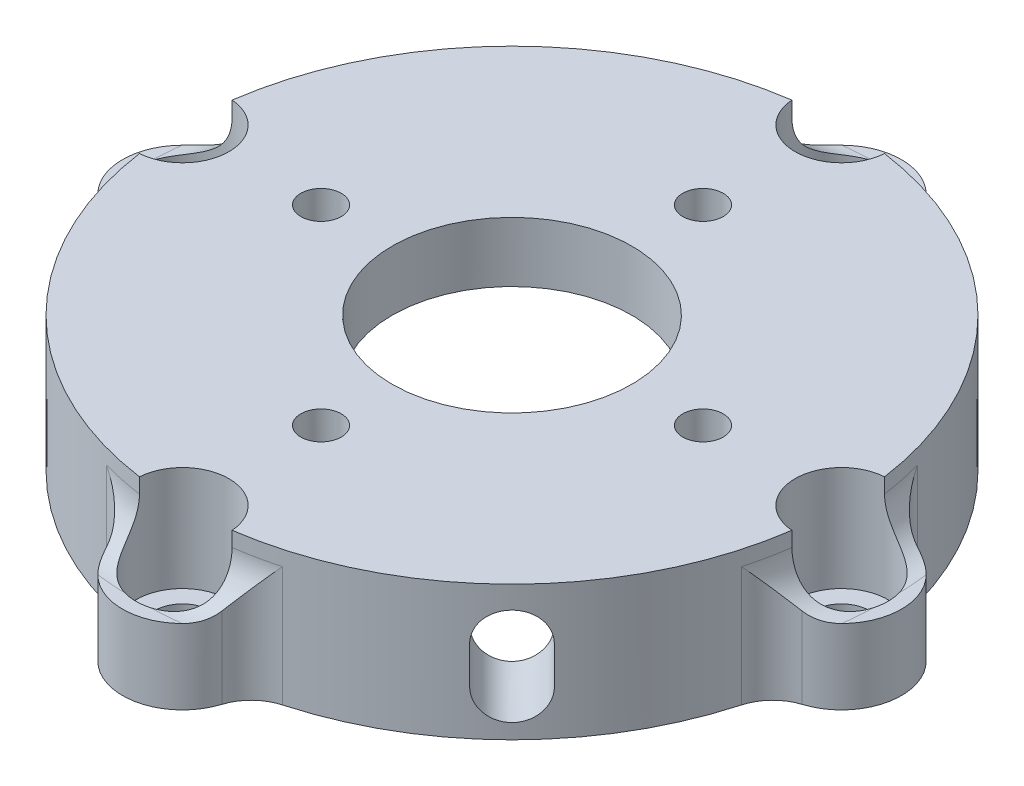
SolidWorks part; units mm, degrees
note: The reader was unsure of these and kept them because the rebuilt part matched: shared geometry of "Sketch4<5>", "Sketch4<6>", "Sketch4<7>", "Sketch5<4>".
ref_plane "Front Plane" through (0, 0, 0) normal (0, 0, 1) x (1, 0, 0)
ref_plane "Top Plane" through (0, 0, 0) normal (0, 1, 0) x (1, 0, 0)
ref_plane "Right Plane" through (0, 0, 0) normal (1, 0, 0) x (0, 0, -1)
sketch "Sketch1" plane through (0, 0, 0) normal (0, 1, 0) x (1, 0, 0)
  circle A0 centre (0, 0) radius 22
  circle A1 centre (0, 0) radius 8
  dimension "D1" = 44
  dimension "D2" = 16
extrude "Boss-Extrude1" add sketch "Sketch1" against normal blind 4
sketch "Sketch2" plane through (0, -4, 0) normal (0, -1, 0) x (1, 0, 0)
  circle A0 centre (0, 0) radius 22
  circle A1 centre (0, 0) radius 22 construction
  circle A2 centre (0, 0) radius 17
  dimension "D1" = 5
extrude "Boss-Extrude4" add sketch "Sketch2" along normal blind 5
sketch "Sketch4" plane through (0, -9, 0) normal (0, -1, 0) x (1, 0, 0)
  circle A0 centre (0, 0) radius 22 construction
  circle A1 centre (0, 22) radius 3.1
  circle A2 centre (0, 22) radius 1.85
  circle A3 centre (0, 22) radius 4
  dimension "D1" = 44
  dimension "D2" = 6.2
  dimension "D3" = 3.7
  dimension "D4" = 8
extrude "Boss-Extrude2" add sketch "Sketch4" against normal blind 5
extrude "Boss-Extrude3" add sketch "Sketch4<5>" against normal blind 2
sketch "Sketch4<5>" plane through (0, -9, 0) normal (0, -1, 0) x (1, 0, 0) same geometry as "Sketch4"
extrude "Cut-Extrude3" cut sketch "Sketch4<6>" against normal through all from surface at -2 starting at face at (0, -7, 23.1679)
sketch "Sketch4<6>" plane through (0, -9, 0) normal (0, -1, 0) x (1, 0, 0) same geometry as "Sketch4"
extrude "Cut-Extrude4" cut sketch "Sketch4<7>" against normal through all
sketch "Sketch4<7>" plane through (0, -9, 0) normal (0, -1, 0) x (1, 0, 0) same geometry as "Sketch4"
sketch "Sketch5" plane through (0, 0, 0) normal (0, 1, 0) x (1, 0, 0)
  line L1 (2.3671, 12.75) -> (1.1836, 14.8)
  line L2 (1.1836, 14.8) -> (-1.1836, 14.8)
  line L3 (-1.1836, 14.8) -> (-2.3671, 12.75)
  line L4 (-2.3671, 12.75) -> (-1.1836, 10.7)
  line L5 (-1.1836, 10.7) -> (1.1836, 10.7)
  line L6 (1.1836, 10.7) -> (2.3671, 12.75)
  circle A0 centre (0, 0) radius 12.75 construction
  circle A1 centre (0, 12.75) radius 1.35
  circle A2 centre (0, 12.75) radius 2.05 construction
  dimension "D1" = 25.5
  dimension "D2" = 2.7
  dimension "D3" = 4.1
extrude "Cut-Extrude5" cut sketch "Sketch5" against normal up to next contours A1
extrude "Cut-Extrude7" cut sketch "Sketch5<4>" along normal blind 2 from surface at -4 starting at face at (0, -4, -11.4)
sketch "Sketch5<4>" plane through (0, 0, 0) normal (0, 1, 0) x (1, 0, 0) same geometry as "Sketch5"
fillet "Fillet4" radius 3 4 edges at (3.9834, -6.5, 21.6364) (-3.9834, -6.5, 21.6364) (3.5386, -4, 21.7135) (-3.5386, -4, 21.7135)
pattern_circular "CirPattern3" count 4 over 360 about axis through (0, 0, 0) along (0, 1, 0) of "Cut-Extrude5", "Cut-Extrude4", "Cut-Extrude3", "Boss-Extrude3", "Boss-Extrude2", "Cut-Extrude7", "Fillet4"
ref_plane "Plane2" through (6.375, 0, 6.375) normal (0.7071, 0, 0.7071) x (0.7071, 0, -0.7071)
sketch "Sketch7" plane through (6.375, 0, 6.375) normal (0.7071, 0, 0.7071) x (0.7071, 0, -0.7071)
  line L0 (0, -6) -> (0, -3.5) construction
  line L1 (0, -9) -> (0, -1) construction
  line L2 (-2, -6) -> (-2, -3.5)
  line L3 (2, -6) -> (2, -3.5)
  line L6 (13.2153, 0) -> (-13.2153, 0) construction
  arc A0 (-2, -6) -> (2, -6) centre (0, -6) ccw
  arc A1 (2, -3.5) -> (-2, -3.5) centre (0, -3.5) ccw
  point P5 (0, -4.75)
  dimension "D1" = 2
  dimension "D2" = 3.5
  dimension "D3" = 2.5
extrude "Cut-Extrude8" cut sketch "Sketch7" along normal up to next and the other way up to next
equation "\"D2@Sketch7\"=\"D1@Sketch7\"+1.5"
